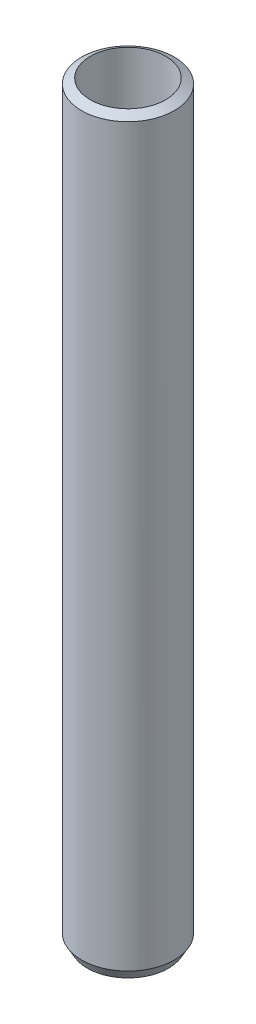
SolidWorks part; units mm, degrees
ref_plane "Front Plane" through (0, 0, 0) normal (0, 0, 1) x (1, 0, 0)
ref_plane "Top Plane" through (0, 0, 0) normal (0, 1, 0) x (1, 0, 0)
ref_plane "Right Plane" through (0, 0, 0) normal (1, 0, 0) x (0, 0, -1)
sketch "Sketch1" plane through (0, 0, 0) normal (0, 1, 0) x (1, 0, 0)
  circle A0 centre (0, 0) radius 25
  dimension "SHAFT_OD" = 50
extrude "Boss-Extrude1" add sketch "Sketch1" along normal blind 404.7849
sketch "Sketch2" plane through (0, 0, 0) normal (0, 1, 0) x (1, 0, 0)
  circle A0 centre (0, 0) radius 20.3121
  dimension "BORE_D" = 40.6241
extrude "Cut-Extrude1" cut sketch "Sketch2" along normal through all
chamfer "Chamfer1" distance 3.1446 angle 60 2 edges at (0, 404.7849, 25) (0, 0, 25) first distance on face at (0, 404.7849, 25) first distance on face at (0, 0, 20.3121)
